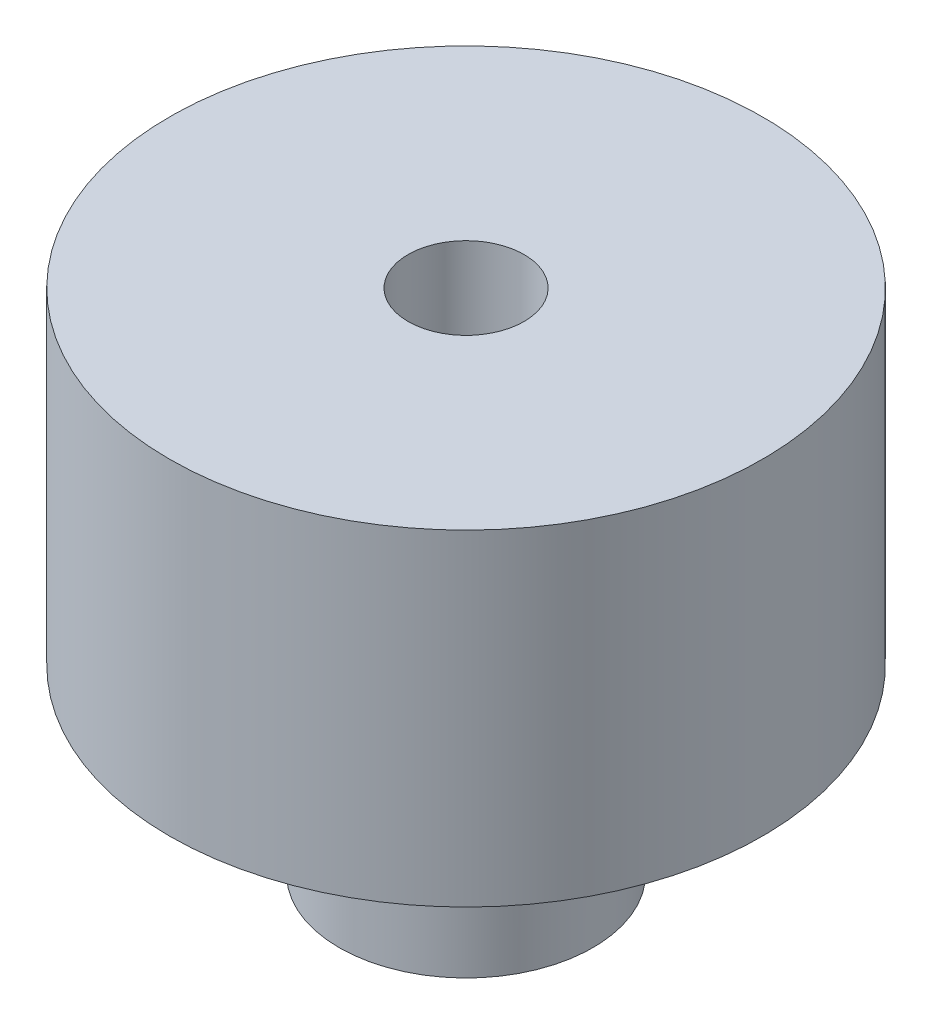
SolidWorks part; units mm, degrees
ref_plane "Front Plane" through (0, 0, 0) normal (0, 0, 1) x (1, 0, 0)
ref_plane "Top Plane" through (0, 0, 0) normal (0, 1, 0) x (1, 0, 0)
ref_plane "Right Plane" through (0, 0, 0) normal (1, 0, 0) x (0, 0, -1)
sketch "Sketch1" plane through (0, 0, 0) normal (0, 1, 0) x (1, 0, 0)
  circle A0 centre (0, 0) radius 1.6
  circle A1 centre (0, 0) radius 8.175
  circle A2 centre (0, 0) radius 8.175
  point P25 (0, 0)
extrude "Boss-Extrude1" add sketch "Sketch1" along normal blind 6 and the other way blind 3 contours A1 A0 region at (-7.9438, 0, 0)
extrude "Boss-Extrude2" add sketch "Sketch1<3>" against normal blind 3 separate body contours A2 A1 region at (-7.9438, 0, 0)
sketch "Sketch1<3>" plane through (0, 0, 0) normal (0, 1, 0) x (1, 0, 0) same geometry as "Sketch1"
sketch "Sketch2" plane through (0, 0, 0) normal (1, 0, 0) x (0, 0, -1)
  line L0 (0, 0) -> (0, 2)
  line L1 (0, 4) -> (0, 6)
  circle A0 centre (0, 3) radius 1
  dimension "D1" = 2
extrude "Cut-Extrude1" cut sketch "Sketch2" against normal blind 15 contours A0
sketch "Sketch3" plane through (0, -3, 0) normal (0, -1, 0) x (1, 0, 0)
  circle A0 centre (0, 9.6613) radius 0.75
  circle A2 centre (9.1884, 2.9855) radius 0.75
  circle A3 centre (5.6787, -7.8161) radius 0.75
  circle A4 centre (-5.6787, -7.8161) radius 0.75
  circle A5 centre (-9.1884, 2.9855) radius 0.75
  point P14 (0, 0)
  dimension "D1" = 5
sketch "Sketch4" plane through (0, -3, 0) normal (0, -1, 0) x (1, 0, 0)
  circle A0 centre (0, 0) radius 3.5
extrude "Boss-Extrude3" add sketch "Sketch4" along normal blind 5 contours A0
extrude "Cut-Extrude2" cut sketch "Sketch1<7>" against normal blind 13 contours A0
sketch "Sketch1<7>" plane through (0, 0, 0) normal (0, 1, 0) x (1, 0, 0) same geometry as "Sketch1"
extrude "Cut-Extrude3" [suppressed] cut sketch "Sketch3" against normal blind 10
